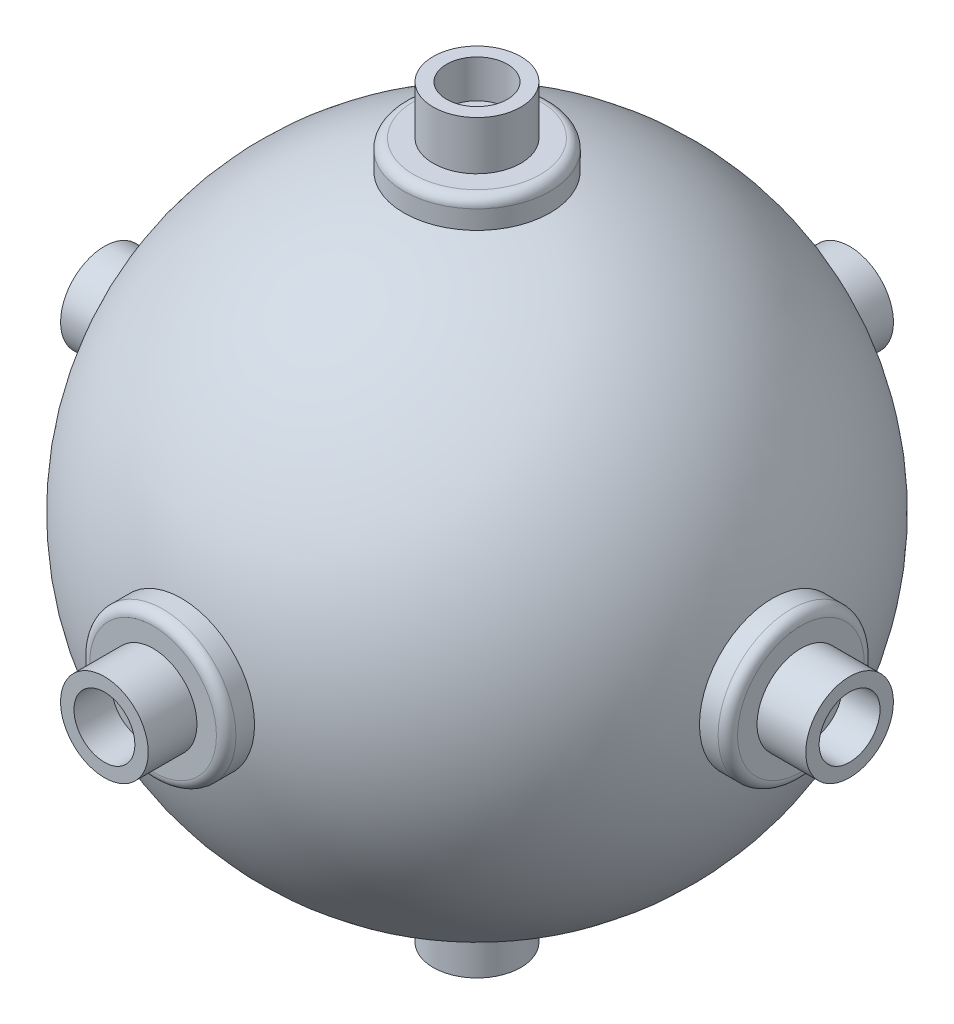
SolidWorks part; units mm, degrees
material "ABS"
ref_plane "Front Plane" through (0, 0, 0) normal (0, 0, 1) x (1, 0, 0)
ref_plane "Top Plane" through (0, 0, 0) normal (0, 1, 0) x (1, 0, 0)
ref_plane "Right Plane" through (0, 0, 0) normal (1, 0, 0) x (0, 0, -1)
sketch "Sketch1" plane through (0, 0, 0) normal (0, 0, 1) x (1, 0, 0)
  line L0 (0, 15.875) -> (0, -15.875)
  arc A0 (0, 15.875) -> (0, -15.875) centre (0, 0) ccw
revolve "Revolve1" add sketch "Sketch1" angle 360 about L0 region at (-6.7376, 0, 0)
sketch "Sketch2" plane through (0, 0, 0) normal (0, 0, 1) x (1, 0, 0)
  circle A0 centre (0, 0) radius 15.875 construction
  point P0 (0, 15.875)
  point P1 (0, -15.875)
  point P4 (15.875, 0)
  point P5 (-15.875, 0)
sketch "Sketch5" plane through (0, 0, 0) normal (1, 0, 0) x (0, 0, -1)
  circle A0 centre (0, 0) radius 15.875 construction
  point P0 (-15.875, 0)
  point P1 (15.875, 0)
ref_plane "Plane2" through (0, 0, 15.875) normal (0, 0, 1) x (1, 0, 0)
sketch "Sketch6" plane through (0, 0, 15.875) normal (0, 0, 1) x (1, 0, 0)
  circle A0 centre (0, 0) radius 3.81
extrude "Boss-Extrude1" add sketch "Sketch6" along normal mid plane 2.032 contours A0
sketch "Sketch7" plane through (0, 0, 0) normal (0, 0, 1) x (1, 0, 0)
  line L0 (0, 15.875) -> (0, -15.875) construction
sketch "Sketch9" plane through (0, 0, 16.891) normal (0, 0, 1) x (1, 0, 0)
  circle A0 centre (0, 0) radius 2.286
extrude "Boss-Extrude3" add sketch "Sketch9" along normal blind 2.54
pattern_circular "CirPattern1" count 4 over 360 about axis through (0, 15.875, 0) along (0, -1, 0) of "Boss-Extrude1", "Boss-Extrude3"
ref_plane "Plane3" through (0, 15.875, 0) normal (0, 1, 0) x (1, 0, 0)
sketch "Sketch10" plane through (0, 15.875, 0) normal (0, 1, 0) x (1, 0, 0)
  circle A0 centre (0, 0) radius 3.81
extrude "Boss-Extrude4" add sketch "Sketch10" along normal mid plane 2.032
sketch "Sketch11" plane through (0, 16.891, 0) normal (0, 1, 0) x (1, 0, 0)
  circle A0 centre (0, 0) radius 2.286
extrude "Boss-Extrude5" add sketch "Sketch11" along normal blind 2.54
mirror "Mirror1" about plane through (0, 0, 0) normal (0, 1, 0) of "Boss-Extrude4", "Boss-Extrude5"
hole_wizard "CBORE for #00 Binding Head Machine Screw1" positions "Sketch12" profile "Sketch13" counterbore size "#00" standard "ANSI Inch"
sketch "Sketch12" plane through (0, 19.431, 0) normal (0, 1, 0) x (1, 0, 0)
  point P0 (0, 0)
sketch "Sketch13" plane through (0, 19.431, 0) normal (1, 0, 0) x (0, 0, 1)
  line L0 (0, 0) -> (0, 4.2297)
  line L1 (0, 4.2297) -> (0.6985, 3.81)
  line L2 (0.6985, 3.81) -> (0.6985, 1.9812)
  line L3 (0.6985, 1.9812) -> (1.5875, 1.9812)
  line L4 (1.5875, 1.9812) -> (1.5875, 0)
  line L5 (1.5875, 0) -> (0, 0)
  line L10 (0, 4.2297) -> (-0.6985, 3.81) construction
  line L11 (0, -6.35) -> (0, 107.95) construction
  dimension "Hole Dia." = 1.397
  dimension "Hole Depth" = 3.81
  dimension "C'Bore Dia." = 3.175
  dimension "C'Bore Depth" = 1.9812
  dimension "Drill Angle" = 118
sketch "Sketch15" plane through (0, 0, 0) normal (0, 1, 0) x (1, 0, 0)
  line L0 (-15.875, 0) -> (15.875, 0) construction
pattern_circular "CirPattern2" count 4 every 90 about axis through (-15.875, 0, 0) along (1, 0, 0) of "CBORE for #00 Binding Head Machine Screw1" reverse direction yes
hole_wizard "CBORE for #00 Binding Head Machine Screw3" positions "Sketch18" profile "Sketch19" counterbore size "#00" standard "ANSI Inch"
sketch "Sketch18" plane through (19.431, 0, 0) normal (1, 0, 0) x (0, 0, -1)
  point P0 (0, 0)
sketch "Sketch19" plane through (19.431, 0, 0) normal (0, 1, 0) x (0, 0, -1)
  line L0 (0, 0) -> (0, 4.2297)
  line L1 (0, 4.2297) -> (0.6985, 3.81)
  line L2 (0.6985, 3.81) -> (0.6985, 1.9812)
  line L3 (0.6985, 1.9812) -> (1.5875, 1.9812)
  line L4 (1.5875, 1.9812) -> (1.5875, 0)
  line L5 (1.5875, 0) -> (0, 0)
  line L10 (0, 4.2297) -> (-0.6985, 3.81) construction
  line L11 (0, -6.35) -> (0, 107.95) construction
  dimension "Hole Dia." = 1.397
  dimension "Hole Depth" = 3.81
  dimension "C'Bore Dia." = 3.175
  dimension "C'Bore Depth" = 1.9812
  dimension "Drill Angle" = 118
mirror "Mirror2" about plane through (0, 0, 0) normal (1, 0, 0) of "CBORE for #00 Binding Head Machine Screw3"
fillet "Fillet1" radius 0.508 6 edges at (-3.81, 0, -16.891) (0, -16.891, 3.81) (-16.891, 0, 3.81) (16.891, 0, -3.81) (3.81, 0, 16.891) (0, 16.891, 3.81)
